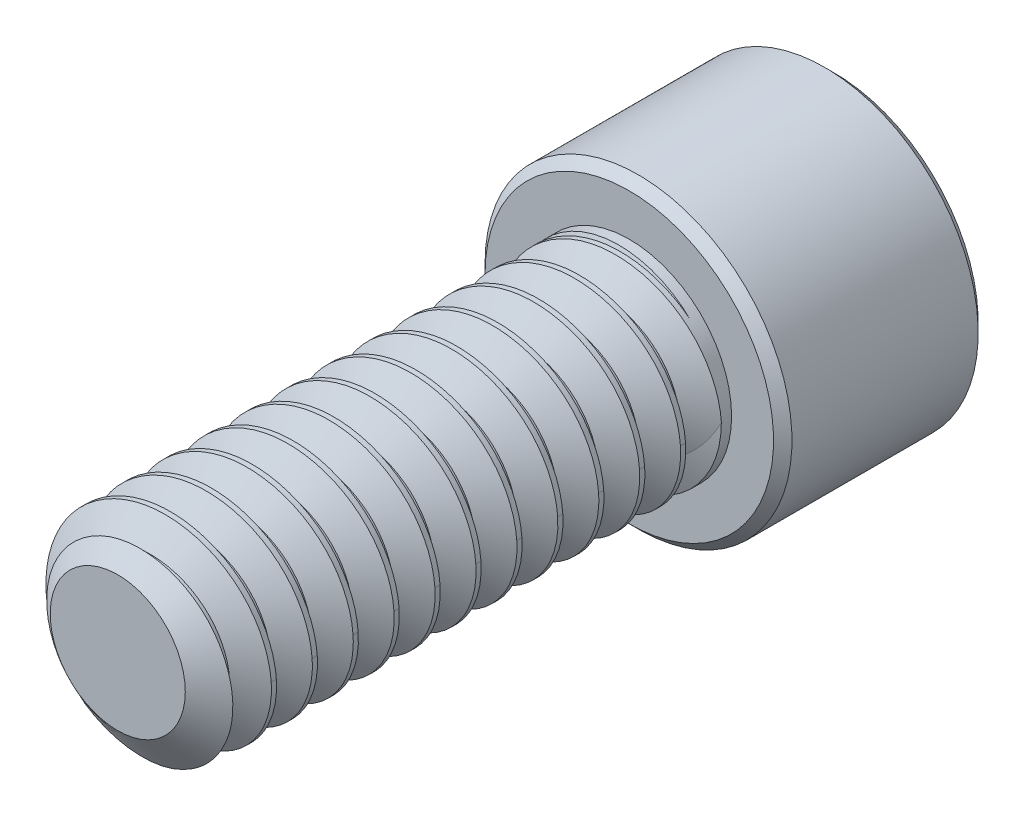
SolidWorks part; units mm, degrees
ref_plane "Front Plane" through (0, 0, 0) normal (0, 0, 1) x (1, 0, 0)
ref_plane "Top Plane" through (0, 0, 0) normal (0, 1, 0) x (1, 0, 0)
ref_plane "Right Plane" through (0, 0, 0) normal (1, 0, 0) x (0, 0, -1)
sketch "Sketch1" plane through (0, 0, 0) normal (0, 0, 1) x (1, 0, 0)
  circle A0 centre (0, 0) radius 3.175
  dimension "OD" = 6.35
extrude "Extrude1" add sketch "Sketch1" against normal blind 15.875
sketch "Sketch2" plane through (0, 0, 0) normal (0, 0, 1) x (1, 0, 0)
  circle A0 centre (0, 0) radius 3.175 construction
  circle A1 centre (0, 0) radius 3.175
curve "Helix/Spiral1" pitch 1.27 height 17.145 turns 13.5 parameters "pitch"=1.27
sketch "Sketch3" plane through (0, 0, 0) normal (1, 0, 0) x (0, 0, -1)
  line L0 (-1.1113, 3.175) -> (-0.635, 2.3501)
  line L1 (-0.635, 2.3501) -> (-0.4763, 2.3501)
  line L2 (-0.4763, 2.3501) -> (0, 3.175)
  line L3 (-1.1113, 3.175) -> (0, 3.175)
  line L4 (-0.5556, 3.175) -> (-0.5556, 2.3501) construction
  line L5 (-0.8731, 2.7626) -> (-0.2381, 2.7626) construction
  line L6 (0, 3.175) -> (0, -3.175) construction
  line L7 (0, -3.175) -> (15.875, -3.175) construction
  point P11 (5.715, -3.175)
  dimension "D1" = 0.1588
  dimension "D2" = 0.635
  dimension "D3" = 60
  dimension "D4" = 5.715
sweep "Cut-Sweep1" cut profiles "Sketch3" path "Helix/Spiral1"
sketch "Sketch4" plane through (0, 0, 0) normal (1, 0, 0) x (0, 0, -1)
  line L0 (0.7554, 3.175) -> (0, 2.0961)
  line L1 (0, 2.0961) -> (0, 3.175)
  line L2 (0.7554, 3.175) -> (0, 3.175)
  line L3 (-1.1113, 3.175) -> (0, 3.175) construction
  line L4 (0, 0) -> (7.0209, 0) construction
  dimension "D1" = 55
  dimension "D2" = 0.254
revolve "Cut-Revolve1" cut sketch "Sketch4" angle 360 about L4
sketch "Sketch5" plane through (0, 0, 0) normal (1, 0, 0) x (0, 0, -1)
  line L0 (15.875, -2.2654) -> (15.875, 2.3728) construction
  line L1 (15.875, 3.175) -> (0.1202, 3.175)
  line L2 (15.875, 3.175) -> (15.875, 0)
  line L3 (15.875, 0) -> (0, 0)
  line L4 (0, 2.8448) -> (0, 0)
  line L5 (0.1202, 3.175) -> (0, 2.8448)
  line L6 (0, 0) -> (9.9695, 0) construction
  point P3 (0, 3.175)
  point P10 (0, 3.175)
  dimension "D1" = 0.3302
  dimension "D3" = 20
  dimension "Thread Min" = 0
revolve "partially thread" [suppressed] add sketch "Sketch5" angle 360 about L6
sketch "Sketch6" plane through (0, 0, -15.875) normal (0, 0, -1) x (-1, 0, 0)
  circle A0 centre (0, 0) radius 4.7625
  dimension "head dia" = 9.525
extrude "Extrude2" add sketch "Sketch6" along normal blind 6.35
sketch "Sketch7" plane through (0, 0, -22.225) normal (0, 0, -1) x (-1, 0, 0)
  line L1 (0, 2.7496) -> (-2.3813, 1.3748)
  line L2 (-2.3813, 1.3748) -> (-2.3813, -1.3748)
  line L3 (-2.3813, -1.3748) -> (0, -2.7496)
  line L4 (0, -2.7496) -> (2.3813, -1.3748)
  line L5 (2.3813, -1.3748) -> (2.3813, 1.3748)
  line L6 (2.3813, 1.3748) -> (0, 2.7496)
  circle A0 centre (0, 0) radius 2.3813 construction
  dimension "hex dia" = 4.7625
extrude "Cut-Extrude1" cut sketch "Sketch7" against normal blind 3.5719
sketch "Sketch8" plane through (0, 0, -22.225) normal (0, 0, -1) x (-1, 0, 0)
  circle A0 centre (0, 0) radius 2.7496
extrude "Cut-Extrude2" cut sketch "Sketch8" against normal through all draft 45
chamfer "Chamfer1" distance 0.2858 angle 45 2 edges at (-4.7625, 0, -22.225) (-4.7625, 0, -15.875)
sketch "Sketch9" plane through (0, 0, 0) normal (1, 0, 0) x (0, 0, -1)
  line L0 (0, 3.175) -> (0, -3.175) construction
  line L1 (6.985, 3.175) -> (6.985, -3.175) construction
  dimension "D1" = 6.985
sketch "Sketch10" plane through (0, 0, 0) normal (1, 0, 0) x (0, 0, -1)
  line L0 (15.875, 3.175) -> (15.875, 0)
  line L1 (15.875, 3.175) -> (15.5575, 3.175)
  line L2 (15.5575, 3.175) -> (14.2424, 0)
  line L3 (15.875, 0) -> (14.2424, 0)
  line L4 (15.875, 4.4768) -> (15.875, -4.4768) construction
  dimension "D1" = 22.5
  dimension "D2" = 0.3175
revolve "Revolve1" add sketch "Sketch10" angle 360 about L3
equation "\"D3@Helix/Spiral1\" = \"screw length@Extrude1\"+\"pitch@Helix/Spiral1\""
equation "\"D1@Sketch3\" = \"pitch@Helix/Spiral1\"*.125"
equation "\"D2@Sketch3\" = \"pitch@Helix/Spiral1\"*.5"
equation "\"D1@Cut-Extrude1\" = \"hex dia@Sketch7\"*.75"
equation "\"D1@Chamfer1\" = \"head dia@Sketch6\"*.03"
equation "\"D1@Sketch9\" = \"pitch@Helix/Spiral1\"*5.5"
equation "\"D2@Sketch10\" = \"pitch@Helix/Spiral1\"*.25"
equation "\"D4@Sketch3\" = \"pitch@Helix/Spiral1\"*4.50"
